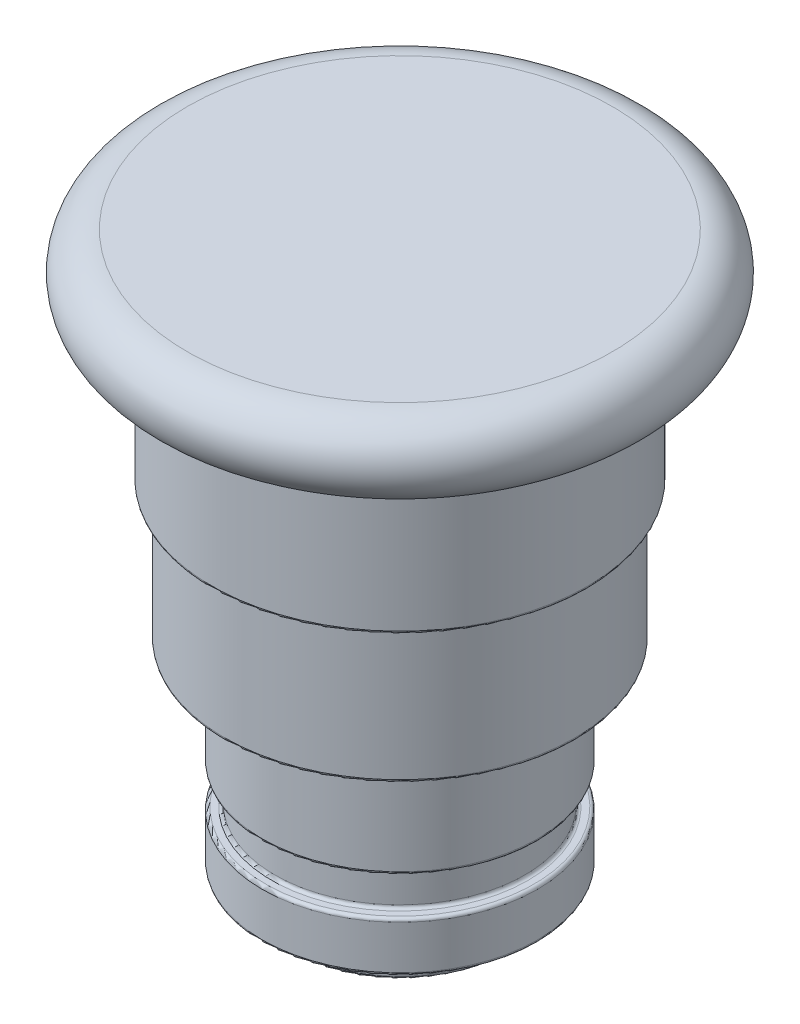
SolidWorks part; units mm, degrees
ref_plane "Plan de face" through (0, 0, 0) normal (0, 0, 1) x (1, 0, 0)
ref_plane "Plan de dessus" through (0, 0, 0) normal (0, 1, 0) x (1, 0, 0)
ref_plane "Plan de droite" through (0, 0, 0) normal (1, 0, 0) x (0, 0, -1)
sketch "Esquisse1" plane through (0, 0, 0) normal (0, 0, 1) x (1, 0, 0)
  line L0 (-11, 2) -> (-8.5, 2)
  line L1 (0, 0) -> (-8.5, 0)
  line L2 (0, 40) -> (0, 0) construction
  line L3 (-11, 9) -> (-11, 17.5)
  line L4 (-11, 2) -> (-11, 6)
  line L5 (-8.5, 2) -> (-8.5, 0)
  line L6 (0, 0) -> (0, 40)
  line L7 (-11, 6) -> (-10, 6)
  line L8 (-15, 40) -> (-17, 40)
  line L9 (-11, 9) -> (-10, 9)
  line L10 (-10, 6) -> (-10, 9)
  line L11 (-11, 17.5) -> (-14, 17.5)
  line L12 (-17, 46) -> (0, 46)
  line L13 (0, 46) -> (0, 40)
  line L14 (-14, 17.5) -> (-14, 28.5)
  line L15 (-14, 28.5) -> (-15, 28.5)
  line L16 (-15, 40) -> (0, 40) construction
  line L18 (-15, 28.5) -> (-15, 40)
  arc A0 (-17, 46) -> (-17, 40) centre (-17, 43) ccw
  dimension "D13" = 6
  dimension "D2" = 1
  dimension "D3" = 3
  dimension "D4" = 2
  dimension "D5" = 4
  dimension "D6" = 3
  dimension "D7" = 11
  dimension "D8" = 8.5
  dimension "D9" = 1
  dimension "D10" = 15
  dimension "D11" = 40
  dimension "D12" = 8.5
  dimension "D14" = 17
revolve "Révolution1" add sketch "Esquisse1" angle 360 about L2
fillet "Congé1" radius 2 1 edges at (-15, 40, 0)
fillet "Congé2" radius 0.25 11 edges at (-10, 6, 0) (-8.5, 0, 0) (-8.5, 2, 0) (-11, 6, 0) (-11, 2, 0) (-10, 9, 0) (-11, 9, 0) (-11, 17.5, 0) (-14, 17.5, 0) (-14, 28.5, 0) (-15, 28.5, 0)
